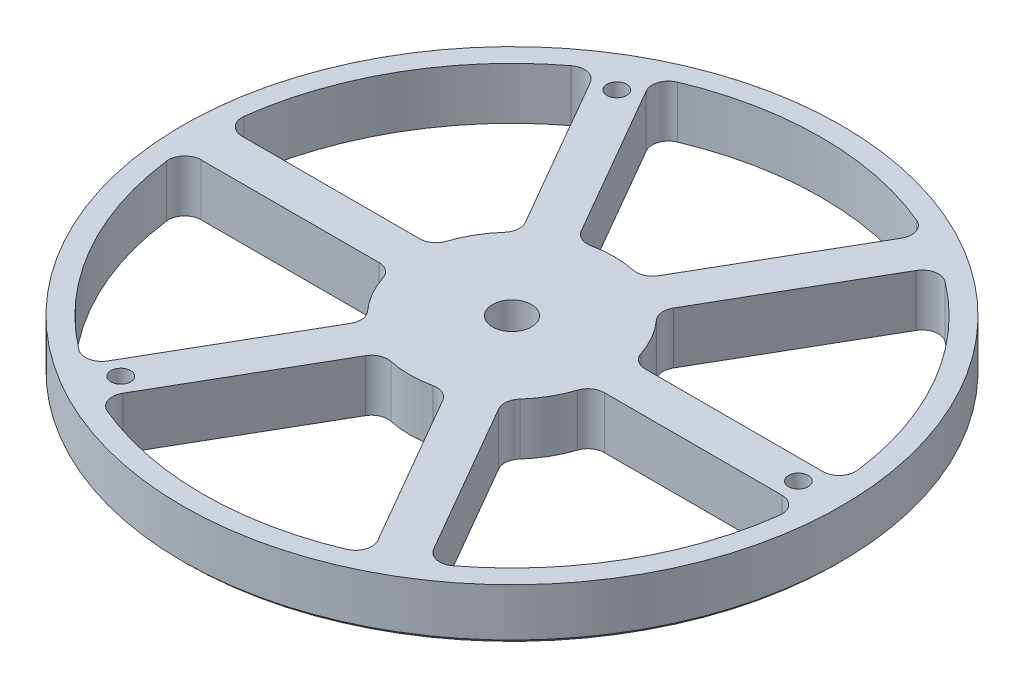
SolidWorks part; units mm, degrees
material "6061-T6 (SS)"
ref_plane "Front Plane" through (0, 0, 0) normal (0, 0, 1) x (1, 0, 0)
ref_plane "Top Plane" through (0, 0, 0) normal (0, 1, 0) x (1, 0, 0)
ref_plane "Right Plane" through (0, 0, 0) normal (1, 0, 0) x (0, 0, -1)
sketch "Sketch2" plane through (0, 0, 0) normal (1, 0, 0) x (0, 0, -1)
  line L0 (0, 0) -> (-80.55, 0)
  line L1 (-80.55, 0) -> (-80.55, 12.7)
  line L2 (-80.55, 12.7) -> (0, 12.7)
  line L5 (0, 12.7) -> (0, 0)
  dimension "D1" = 80.55
  dimension "D2" = 12.7
ref_axis "Axis1" through (0, -0.635, 0) along (0, 1, 0)
revolve "Revolve1" add sketch "Sketch2" angle 360 about axis through (0, -0.635, 0) along (0, 1, 0)
hole_wizard "#12 (0.189) Diameter Hole1" positions "Sketch6" profile "Sketch7" hole size "#12" standard "ANSI Inch" end condition through all
sketch "Sketch6" plane through (0, 12.7, 0) normal (0, 1, 0) x (1, 0, 0)
  line L0 (0, 0) -> (-69.8201, 120.932) construction
  line L2 (0, 0) -> (0, 109.0908) construction
  point P0 (-35, 60.6218)
  dimension "D1" = 30
  dimension "D2" = 70
sketch "Sketch7" plane through (-35, 12.7, -60.6218) normal (1, 0, 0) x (0, 0, 1)
  line L0 (0, 0) -> (0, 12.7)
  line L1 (0, 12.7) -> (2.4003, 12.7)
  line L2 (2.4003, 12.7) -> (2.4003, 0)
  line L5 (2.4003, 0) -> (0, 0)
  line L11 (0, -6.35) -> (0, 107.95) construction
  dimension "Thru Hole Dia." = 4.8006
  dimension "Thru Hole Depth" = 12.7
pattern_circular "CirPattern3" count 3 over 360 about axis through (0, -0.635, 0) along (0, 1, 0) of "#12 (0.189) Diameter Hole1"
sketch "Sketch8" plane through (0, 12.7, 0) normal (0, 1, 0) x (1, 0, 0)
  line L4 (0, 0) -> (0, 93.9995) construction
  line L5 (0, 0) -> (113.8372, 0) construction
  line L6 (-7.9173, 23.7132) -> (-33.3621, 67.7848)
  line L7 (7.9173, 23.7132) -> (33.3621, 67.7848)
  line L8 (0, 0) -> (-35, 60.6218) construction
  arc A0 (-7.9173, 23.7132) -> (7.9173, 23.7132) centre (0, 0) cw
  arc A1 (-33.3621, 67.7848) -> (33.3621, 67.7848) centre (0, 0) cw
  circle A2 centre (0, 0) radius 80.55 construction
  dimension "D1" = 25
  dimension "D2" = 5
  dimension "D3" = 5
extrude "Cut-Extrude1" cut sketch "Sketch8" against normal through all
fillet "Fillet1" radius 4 4 edges at (7.9173, 6.35, -23.7132) (33.3621, 6.35, -67.7848) (-7.9173, 6.35, -23.7132) (-33.3621, 6.35, -67.7848)
pattern_circular "CirPattern4" count 6 over 360 about axis through (0, -0.635, 0) along (0, 1, 0) of "Cut-Extrude1", "Fillet1"
chamfer "Chamfer2" distance 1 angle 45 1 edges at (0, 0, -80.55)
hole_wizard "3/8 (0.375) Diameter Hole1" positions "Sketch9" profile "Sketch11" hole size "3/8" standard "ANSI Inch" end condition through all
sketch "Sketch9" plane through (0, 0, 0) normal (0, -1, 0) x (-1, 0, 0)
  point P0 (0, 0)
sketch "Sketch11" plane through (0, 0, 0) normal (1, 0, 0) x (0, 0, -1)
  line L0 (0, 0) -> (0, 12.7)
  line L1 (0, 12.7) -> (4.7625, 12.7)
  line L2 (4.7625, 12.7) -> (4.7625, 0)
  line L5 (4.7625, 0) -> (0, 0)
  line L11 (0, -6.35) -> (0, 107.95) construction
  dimension "Thru Hole Dia." = 9.525
  dimension "Thru Hole Depth" = 12.7
equation "\"TubeDiameter\" = 6.500in"
equation "\"D1@Sketch2\"=(\"TubeDiameter\"-4)/2"
